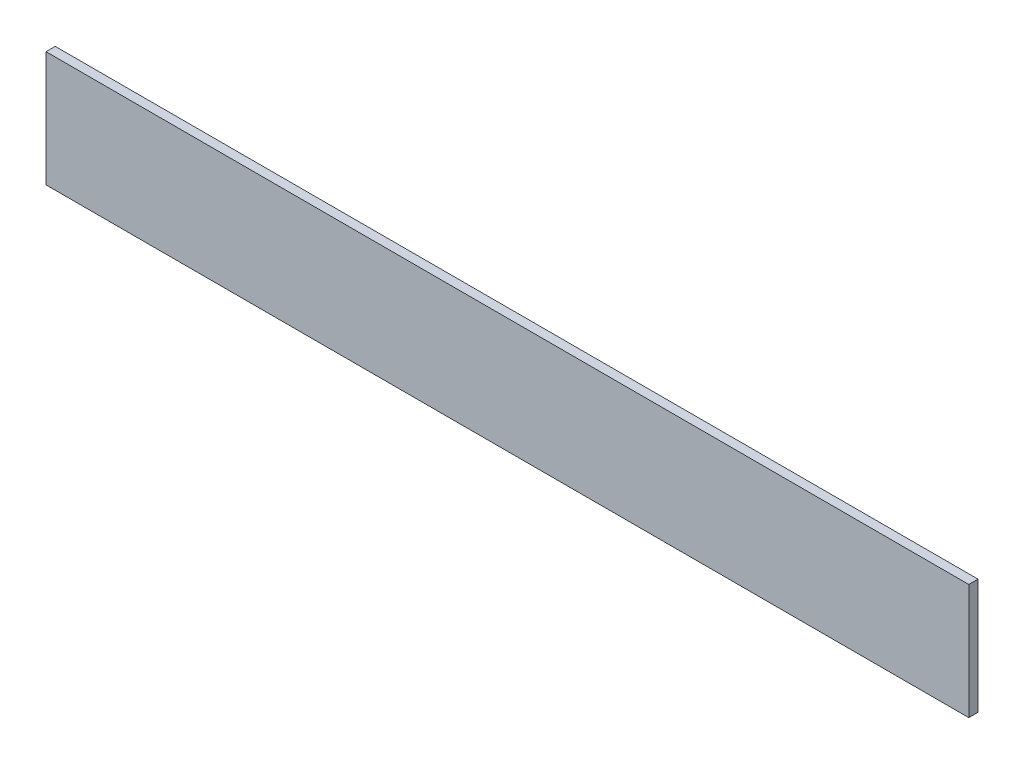
SolidWorks part; units mm, degrees
ref_plane "Спереди" through (0, 0, 0) normal (0, 0, 1) x (1, 0, 0)
ref_plane "Сверху" through (0, 0, 0) normal (0, 1, 0) x (1, 0, 0)
ref_plane "Справа" through (0, 0, 0) normal (1, 0, 0) x (0, 0, -1)
sketch "Эскиз1" plane through (0, 0, 0) normal (1, 0, 0) x (0, 0, -1)
  line L0 (0, 25) -> (0, 0)
  line L1 (0, 0) -> (25, 0)
extrude "Вытянуть-Тонкостенный1" add sketch "Эскиз1" along normal blind 200 thin thin type one direction reverse wall 2
sketch "Эскиз2" plane through (0, 0, 0) normal (0, -1, 0) x (1, 0, 0)
  line L0 (200, -25) -> (0, -25) construction
  line L1 (177, -25) -> (200, -25)
  line L2 (177, -25) -> (177, -2)
  line L3 (177, -2) -> (200, -2)
  line L4 (200, -25) -> (200, -2)
  line L5 (200, 0) -> (200, -25) construction
  dimension "D1" = 23
extrude "Вырез-Вытянуть1" cut sketch "Эскиз2" against normal through all
